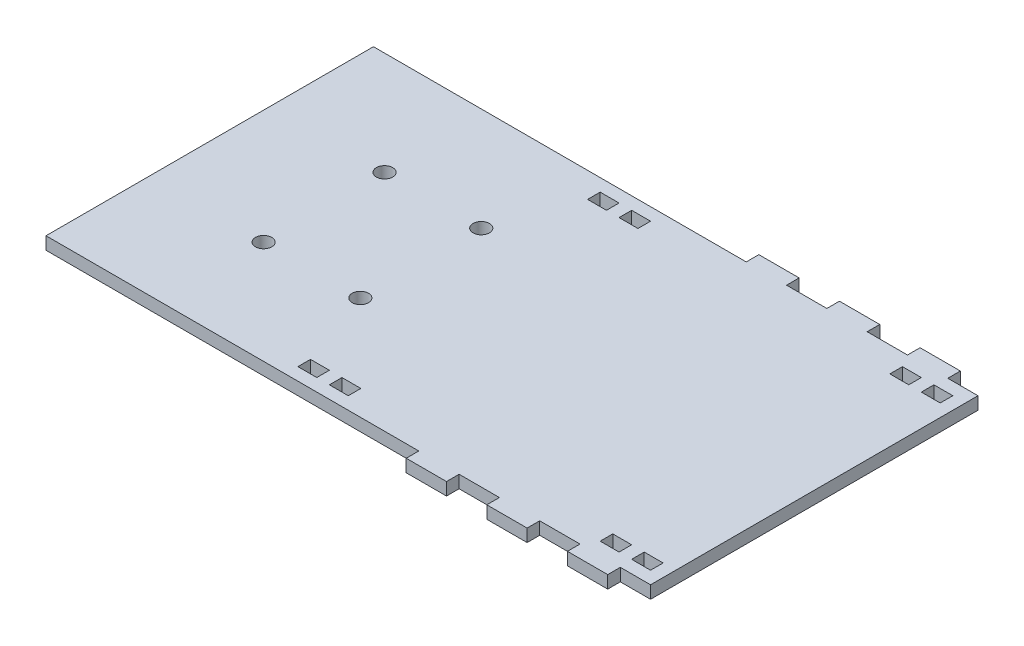
SolidWorks part; units mm, degrees
ref_plane "Front Plane" through (0, 0, 0) normal (0, 0, 1) x (1, 0, 0)
ref_plane "Top Plane" through (0, 0, 0) normal (0, 1, 0) x (1, 0, 0)
ref_plane "Right Plane" through (0, 0, 0) normal (1, 0, 0) x (0, 0, -1)
sketch "Sketch1" plane through (0, 0, 0) normal (0, 1, 0) x (1, 0, 0)
  line L0 (38.1, -41.275) -> (48.26, -41.275)
  line L1 (76.2, -41.275) -> (-76.2, -41.275)
  line L2 (76.2, -41.275) -> (76.2, 41.275)
  line L3 (76.2, 41.275) -> (-76.2, 41.275)
  line L4 (-76.2, -41.275) -> (-76.2, 41.275)
  line L5 (76.2, -41.275) -> (-76.2, 41.275) construction
  line L6 (76.2, 41.275) -> (-76.2, -41.275) construction
  line L7 (58.42, -41.275) -> (68.58, -41.275)
  line L8 (58.42, -41.275) -> (58.42, -44.45)
  line L9 (58.42, -44.45) -> (68.58, -44.45)
  line L10 (68.58, -41.275) -> (68.58, -44.45)
  line L11 (38.1, -41.275) -> (38.1, -44.45)
  line L12 (38.1, -44.45) -> (48.26, -44.45)
  line L13 (48.26, -41.275) -> (48.26, -44.45)
  line L14 (17.78, -41.275) -> (27.94, -41.275)
  line L15 (17.78, -41.275) -> (17.78, -44.45)
  line L16 (17.78, -44.45) -> (27.94, -44.45)
  line L17 (27.94, -41.275) -> (27.94, -44.45)
  line L18 (58.42, 44.45) -> (68.58, 44.45)
  line L19 (58.42, 44.45) -> (58.42, 41.275)
  line L20 (58.42, 41.275) -> (68.58, 41.275)
  line L21 (68.58, 44.45) -> (68.58, 41.275)
  line L22 (38.1, 44.45) -> (48.26, 44.45)
  line L23 (38.1, 44.45) -> (38.1, 41.275)
  line L24 (38.1, 41.275) -> (48.26, 41.275)
  line L25 (48.26, 44.45) -> (48.26, 41.275)
  line L26 (17.78, 44.45) -> (27.94, 44.45)
  line L27 (17.78, 44.45) -> (17.78, 41.275)
  line L28 (17.78, 41.275) -> (27.94, 41.275)
  line L29 (27.94, 44.45) -> (27.94, 41.275)
  line L30 (58.42, -41.275) -> (38.1, -41.275) construction
  point P0 (0, 0)
  dimension "D1" = 3.175
  dimension "D2" = 10.16
  dimension "D5" = 20.32
  dimension "D6" = 82.55
  dimension "D7" = 152.4
  dimension "D8" = 7.62
  dimension "D3" = 3
  dimension "D4" = 2
extrude "Boss-Extrude1" add sketch "Sketch1" along normal blind 3.175 contours L17 L1 L15 L16 | L4 L1 L0 L2 L3 | L13 L0 L11 L12 | L29 L26 L27 L3 | L10 L9 L8 L7 | L18 L21 L20 L19 | L22 L25 L24 L23 region at (0, 0, 0) region at (43.18, 0, 42.8625) region at (22.86, 0, 42.8625) region at (22.86, 0, -42.8625)
sketch "Sketch2" plane through (0, 3.175, 0) normal (0, 1, 0) x (1, 0, 0)
  line L0 (-47.3754, 15.24) -> (-47.3754, -15.24) construction
  line L1 (-47.3754, 0) -> (-76.2, 0) construction
  line L2 (-76.2, -41.275) -> (-76.2, 41.275) construction
  circle A0 centre (-47.3754, 15.24) radius 2.0638
  circle A1 centre (-22.9914, 15.24) radius 2.0638
  circle A2 centre (-22.9914, -15.24) radius 2.0638
  circle A3 centre (-47.3754, -15.24) radius 2.0638
  dimension "D4" = 24.384
  dimension "D5" = 4.1275
  dimension "D3" = 30.48
  dimension "D1" = 2
  dimension "D2" = 2
extrude "Caster Mounting Holes" cut sketch "Sketch2" against normal through all
sketch "Sketch3" plane through (0, 3.175, 0) normal (0, 1, 0) x (1, 0, 0)
  line L0 (58.42, 41.275) -> (48.26, 41.275) construction
  line L2 (65.0875, 38.1) -> (65.0875, 34.925)
  line L4 (68.2625, 38.1) -> (68.2625, 34.925)
  line L7 (76.2, -41.275) -> (76.2, 41.275) construction
  line L9 (68.2625, 38.1) -> (73.025, 38.1)
  line L10 (73.025, 38.1) -> (73.025, 34.925)
  line L11 (73.025, 34.925) -> (68.2625, 34.925)
  line L15 (65.0875, 34.925) -> (60.325, 34.925)
  line L16 (60.325, 34.925) -> (60.325, 38.1)
  line L17 (60.325, 38.1) -> (65.0875, 38.1)
  point P0 (66.675, 36.5125)
  dimension "D1" = 3.175
  dimension "D2" = 4.7625
  dimension "D3" = 3.175
  dimension "D4" = 3.175
  dimension "D5" = 3.175
extrude "Cut-Extrude1" cut sketch "Sketch3" against normal through all contours L17 L16 L15 L2 | L11 L10 L9 L4 region at (62.7063, 3.175, -36.5125) region at (70.6438, 3.175, -36.5125)
pattern_linear "LPattern1" count 2 spacing 76.2 along (-1, 0, 0) count 2 spacing 73.025 along (0, 0, 1) of "Cut-Extrude1"
sketch "Sketch4" plane through (0, 3.175, 0) normal (0, 1, 0) x (1, 0, 0)
  line L9 (-11.1887, -38.0238) -> (-11.1887, -35.0012)
  line L10 (-15.7988, -38.0238) -> (-11.1887, -38.0238)
  line L11 (-15.7988, -35.0012) -> (-15.7988, -38.0238)
  line L12 (-11.1887, -35.0012) -> (-15.7988, -35.0012)
  line L13 (-11.1887, -38.0238) -> (-11.1887, -35.0012)
  line L14 (-15.7988, -38.0238) -> (-11.1887, -38.0238)
  line L15 (-15.7988, -35.0012) -> (-15.7988, -38.0238)
  line L16 (-11.1887, -35.0012) -> (-15.7988, -35.0012)
  line L21 (-3.2512, -38.0238) -> (-3.2512, -35.0012)
  line L22 (-3.2512, -35.0012) -> (-7.8613, -35.0012)
  line L23 (-7.8613, -35.0012) -> (-7.8613, -38.0238)
  line L24 (-7.8613, -38.0238) -> (-3.2512, -38.0238)
  line L25 (-3.2512, -38.0238) -> (-3.2512, -35.0012)
  line L26 (-3.2512, -35.0012) -> (-7.8613, -35.0012)
  line L27 (-7.8613, -35.0012) -> (-7.8613, -38.0238)
  line L28 (-7.8613, -38.0238) -> (-3.2512, -38.0238)
  line L33 (60.4012, -38.0238) -> (65.0113, -38.0238)
  line L34 (60.4012, -35.0012) -> (60.4012, -38.0238)
  line L35 (65.0113, -35.0012) -> (60.4012, -35.0012)
  line L36 (65.0113, -38.0238) -> (65.0113, -35.0012)
  line L37 (60.4012, -38.0238) -> (65.0113, -38.0238)
  line L38 (60.4012, -35.0012) -> (60.4012, -38.0238)
  line L39 (65.0113, -35.0012) -> (60.4012, -35.0012)
  line L40 (65.0113, -38.0238) -> (65.0113, -35.0012)
  line L45 (72.9488, -35.0012) -> (68.3387, -35.0012)
  line L46 (68.3387, -35.0012) -> (68.3387, -38.0238)
  line L47 (72.9488, -38.0238) -> (72.9488, -35.0012)
  line L48 (68.3387, -38.0238) -> (72.9488, -38.0238)
  line L49 (72.9488, -35.0012) -> (68.3387, -35.0012)
  line L50 (68.3387, -35.0012) -> (68.3387, -38.0238)
  line L51 (72.9488, -38.0238) -> (72.9488, -35.0012)
  line L52 (68.3387, -38.0238) -> (72.9488, -38.0238)
  line L57 (65.0113, 35.0012) -> (65.0113, 38.0238)
  line L58 (65.0113, 38.0238) -> (60.4012, 38.0238)
  line L59 (60.4012, 38.0238) -> (60.4012, 35.0012)
  line L60 (60.4012, 35.0012) -> (65.0113, 35.0012)
  line L61 (65.0113, 35.0012) -> (65.0113, 38.0238)
  line L62 (65.0113, 38.0238) -> (60.4012, 38.0238)
  line L63 (60.4012, 38.0238) -> (60.4012, 35.0012)
  line L64 (60.4012, 35.0012) -> (65.0113, 35.0012)
  line L69 (72.9488, 35.0012) -> (72.9488, 38.0238)
  line L70 (72.9488, 38.0238) -> (68.3387, 38.0238)
  line L71 (68.3387, 38.0238) -> (68.3387, 35.0012)
  line L72 (68.3387, 35.0012) -> (72.9488, 35.0012)
  line L73 (72.9488, 35.0012) -> (72.9488, 38.0238)
  line L74 (72.9488, 38.0238) -> (68.3387, 38.0238)
  line L75 (68.3387, 38.0238) -> (68.3387, 35.0012)
  line L76 (68.3387, 35.0012) -> (72.9488, 35.0012)
  line L81 (-7.8613, 38.0238) -> (-7.8613, 35.0012)
  line L82 (-3.2512, 38.0238) -> (-7.8613, 38.0238)
  line L83 (-3.2512, 35.0012) -> (-3.2512, 38.0238)
  line L84 (-7.8613, 35.0012) -> (-3.2512, 35.0012)
  line L85 (-7.8613, 38.0238) -> (-7.8613, 35.0012)
  line L86 (-3.2512, 38.0238) -> (-7.8613, 38.0238)
  line L87 (-3.2512, 35.0012) -> (-3.2512, 38.0238)
  line L88 (-7.8613, 35.0012) -> (-3.2512, 35.0012)
  line L93 (-15.7988, 38.0238) -> (-15.7988, 35.0012)
  line L94 (-11.1887, 38.0238) -> (-15.7988, 38.0238)
  line L95 (-11.1887, 35.0012) -> (-11.1887, 38.0238)
  line L96 (-15.7988, 35.0012) -> (-11.1887, 35.0012)
  line L97 (-15.7988, 38.0238) -> (-15.7988, 35.0012)
  line L98 (-11.1887, 38.0238) -> (-15.7988, 38.0238)
  line L99 (-11.1887, 35.0012) -> (-11.1887, 38.0238)
  line L100 (-15.7988, 35.0012) -> (-11.1887, 35.0012)
  line L455 (17.7038, 44.5262) -> (17.7038, 41.3512)
  line L456 (28.0162, 44.5262) -> (17.7038, 44.5262)
  line L457 (28.0162, 41.3512) -> (28.0162, 44.5262)
  line L458 (38.0238, 41.3512) -> (28.0162, 41.3512)
  line L459 (38.0238, 44.5262) -> (38.0238, 41.3512)
  line L460 (48.3362, 44.5262) -> (38.0238, 44.5262)
  line L461 (48.3362, 41.3512) -> (48.3362, 44.5262)
  line L462 (58.3438, 41.3512) -> (48.3362, 41.3512)
  line L463 (58.3438, 44.5262) -> (58.3438, 41.3512)
  line L464 (68.6562, 44.5262) -> (58.3438, 44.5262)
  line L465 (68.6562, 41.3512) -> (68.6562, 44.5262)
  line L466 (76.2762, 41.3512) -> (68.6562, 41.3512)
  line L467 (68.6562, -41.3512) -> (76.2762, -41.3512)
  line L468 (68.6562, -44.5262) -> (68.6562, -41.3512)
  line L469 (58.3438, -44.5262) -> (68.6562, -44.5262)
  line L470 (58.3438, -41.3512) -> (58.3438, -44.5262)
  line L471 (48.3362, -41.3512) -> (58.3438, -41.3512)
  line L472 (48.3362, -44.5262) -> (48.3362, -41.3512)
  line L473 (38.0238, -44.5262) -> (48.3362, -44.5262)
  line L474 (38.0238, -41.3512) -> (38.0238, -44.5262)
  line L475 (28.0162, -41.3512) -> (38.0238, -41.3512)
  line L476 (28.0162, -44.5262) -> (28.0162, -41.3512)
  line L477 (17.7038, -44.5262) -> (28.0162, -44.5262)
  line L478 (17.7038, -41.3512) -> (17.7038, -44.5262)
  line L479 (76.2762, -41.3512) -> (76.2762, 41.3512)
  line L480 (-76.2762, -41.3512) -> (17.7038, -41.3512)
  line L481 (17.7038, 41.3512) -> (-76.2762, 41.3512)
  line L482 (-76.2762, 41.3512) -> (-76.2762, -41.3512)
  line L483 (17.7038, 44.5262) -> (17.7038, 41.3512)
  line L484 (28.0162, 44.5262) -> (17.7038, 44.5262)
  line L485 (28.0162, 41.3512) -> (28.0162, 44.5262)
  line L486 (38.0238, 41.3512) -> (28.0162, 41.3512)
  line L487 (38.0238, 44.5262) -> (38.0238, 41.3512)
  line L488 (48.3362, 44.5262) -> (38.0238, 44.5262)
  line L489 (48.3362, 41.3512) -> (48.3362, 44.5262)
  line L490 (58.3438, 41.3512) -> (48.3362, 41.3512)
  line L491 (58.3438, 44.5262) -> (58.3438, 41.3512)
  line L492 (68.6562, 44.5262) -> (58.3438, 44.5262)
  line L493 (68.6562, 41.3512) -> (68.6562, 44.5262)
  line L494 (76.2762, 41.3512) -> (68.6562, 41.3512)
  line L495 (68.6562, -41.3512) -> (76.2762, -41.3512)
  line L496 (68.6562, -44.5262) -> (68.6562, -41.3512)
  line L497 (58.3438, -44.5262) -> (68.6562, -44.5262)
  line L498 (58.3438, -41.3512) -> (58.3438, -44.5262)
  line L499 (48.3362, -41.3512) -> (58.3438, -41.3512)
  line L500 (48.3362, -44.5262) -> (48.3362, -41.3512)
  line L501 (38.0238, -44.5262) -> (48.3362, -44.5262)
  line L502 (38.0238, -41.3512) -> (38.0238, -44.5262)
  line L503 (28.0162, -41.3512) -> (38.0238, -41.3512)
  line L504 (28.0162, -44.5262) -> (28.0162, -41.3512)
  line L505 (17.7038, -44.5262) -> (28.0162, -44.5262)
  line L506 (17.7038, -41.3512) -> (17.7038, -44.5262)
  line L507 (76.2762, -41.3512) -> (76.2762, 41.3512)
  line L508 (-76.2762, -41.3512) -> (17.7038, -41.3512)
  line L509 (17.7038, 41.3512) -> (-76.2762, 41.3512)
  line L510 (-76.2762, 41.3512) -> (-76.2762, -41.3512)
  circle A2 centre (-47.3754, -15.24) radius 1.9876
  circle A3 centre (-47.3754, -15.24) radius 1.9876
  circle A5 centre (-47.3754, 15.24) radius 1.9876
  circle A6 centre (-47.3754, 15.24) radius 1.9876
  circle A8 centre (-22.9914, 15.24) radius 1.9876
  circle A9 centre (-22.9914, 15.24) radius 1.9876
  circle A11 centre (-22.9914, -15.24) radius 1.9876
  circle A12 centre (-22.9914, -15.24) radius 1.9876
  dimension "D1" = 0.0762
  dimension "D2" = 0.0762
  dimension "D3" = 0.0762
  dimension "D4" = 0.0762
  dimension "D5" = 0.0762
  dimension "D6" = 0.0762
  dimension "D7" = 0.0762
  dimension "D8" = 0.0762
  dimension "D9" = 0.0762
  dimension "D10" = 0.0762
  dimension "D11" = 0.0762
  dimension "D12" = 0.0762
  dimension "D13" = 0.0762
